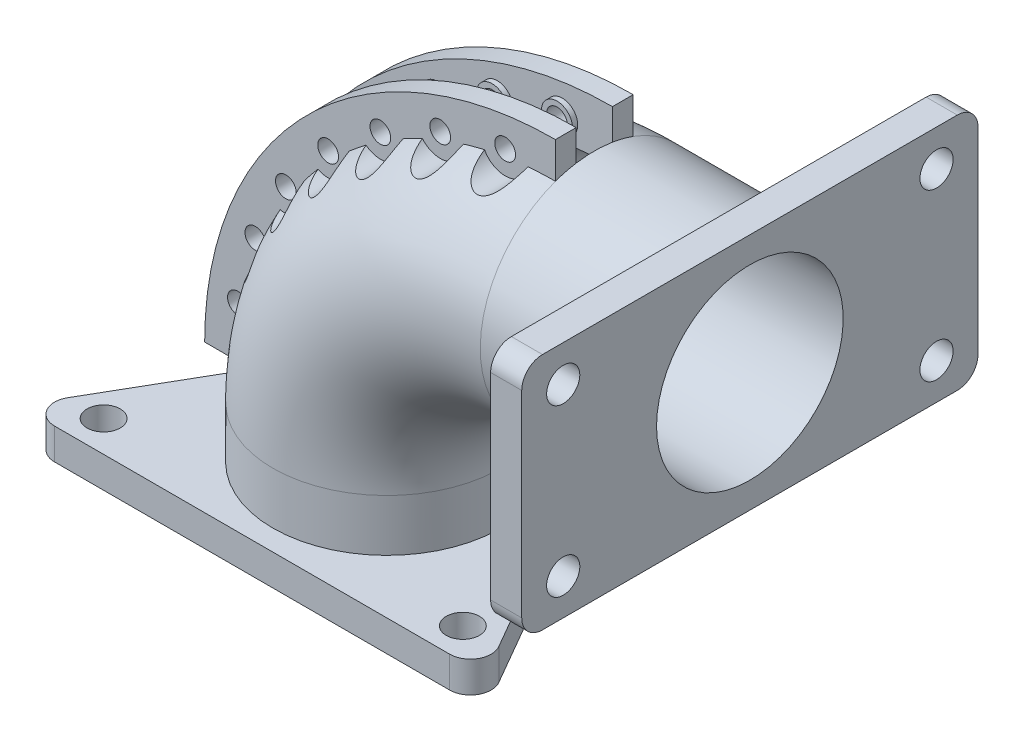
SolidWorks part; units mm, degrees
material "聚脂树脂"
ref_plane "前视基准面" through (0, 0, 0) normal (0, 0, 1) x (1, 0, 0)
ref_plane "上视基准面" through (0, 0, 0) normal (0, 1, 0) x (1, 0, 0)
ref_plane "右视基准面" through (0, 0, 0) normal (1, 0, 0) x (0, 0, -1)
sketch "草图1" plane through (0, 0, 0) normal (0, 1, 0) x (1, 0, 0)
  line L0 (0, 40) -> (0, 0) construction
  line L4 (0, 0) -> (-34.641, -20) construction
  line L5 (0, 0) -> (34.641, -20) construction
  line L6 (-1.7321, 23) -> (-20.7846, -10)
  line L7 (-19.0526, -13) -> (19.0526, -13)
  line L8 (20.7846, -10) -> (1.7321, 23)
  circle A0 centre (0, 0) radius 9
  circle A2 centre (0, 0) radius 20 construction
  circle A3 centre (0, 20) radius 1.6
  circle A4 centre (-17.3205, -10) radius 1.6
  circle A5 centre (17.3205, -10) radius 1.6
  arc A9 (-1.7321, 23) -> (1.7321, 23) centre (0, 22) cw
  arc A10 (19.0526, -13) -> (20.7846, -10) centre (19.0526, -11) ccw
  arc A11 (-20.7846, -10) -> (-19.0526, -13) centre (-19.0526, -11) ccw
  point P18 (0, 26)
  point P21 (22.5167, -13)
  point P24 (-22.5167, -13)
  dimension "D1" = 18
  dimension "D2" = 40
  dimension "D3" = 3.2
  dimension "D4" = 120
  dimension "D5" = 3.2
  dimension "D6" = 120
  dimension "D7" = 3.2
  dimension "D8" = 26
  dimension "D10" = 2
  dimension "D9" = 26
extrude "凸台-拉伸1" add sketch "草图1" along normal blind 3
sketch "草图2" plane through (0, 3, 0) normal (0, 1, 0) x (1, 0, 0)
  circle A0 centre (0, 0) radius 9
  circle A1 centre (0, 0) radius 11
  dimension "D1" = 22
  dimension "D2" = 18
sketch "草图3" plane through (0, 0, 0) normal (0, 0, 1) x (1, 0, 0)
  line L0 (0, 3) -> (0, 8)
  line L1 (11, 3) -> (-11, 3) construction
  line L2 (20, 28) -> (20, 8) construction
  line L3 (20, 28) -> (35, 28)
  arc A0 (0, 8) -> (20, 28) centre (20, 8) cw
  dimension "D1" = 5
  dimension "D2" = 20
  dimension "D3" = 15
sweep "扫描1" add profiles "草图2" path "草图3"
sketch "草图4" plane through (35, 0, 0) normal (1, 0, 0) x (0, 0, -1)
  line L0 (0, 28) -> (0, 37.8313) construction
  line L1 (20, 16.5) -> (-20, 16.5)
  line L2 (22, 18.5) -> (22, 37.5)
  line L3 (20, 39.5) -> (-20, 39.5)
  line L4 (-22, 18.5) -> (-22, 37.5)
  line L5 (22, 16.5) -> (-22, 39.5) construction
  line L6 (22, 39.5) -> (-22, 16.5) construction
  line L7 (0, 28) -> (4.7838, 28) construction
  circle A0 centre (0, 28) radius 9
  circle A1 centre (-18, 36) radius 1.6
  circle A2 centre (18, 36) radius 1.6
  circle A3 centre (-18, 20) radius 1.6
  circle A4 centre (18, 20) radius 1.6
  arc A5 (22, 37.5) -> (20, 39.5) centre (20, 37.5) ccw
  arc A6 (20, 16.5) -> (22, 18.5) centre (20, 18.5) ccw
  arc A7 (-20, 16.5) -> (-22, 18.5) centre (-20, 18.5) cw
  arc A8 (-20, 39.5) -> (-22, 37.5) centre (-20, 37.5) ccw
  dimension "D1" = 18
  dimension "D4" = 3.2
  dimension "D7" = 2
  dimension "D2" = 44
  dimension "D3" = 23
  dimension "D5" = 8
  dimension "D6" = 18
extrude "凸台-拉伸3" add sketch "草图4" against normal blind 3
sketch "草图5" plane through (0, 0, 0) normal (0, 0, 1) x (1, 0, 0)
  line L0 (-11, 8) -> (-11, 3) construction
  line L4 (11, 8) -> (-11, 8) construction
  line L5 (20, 17) -> (20, 39) construction
  line L6 (32, 39) -> (20, 39) construction
  line L7 (-8, 8) -> (-14.303, 8)
  line L8 (20, 47.0087) -> (20, 36)
  arc A0 (-8, 8) -> (20, 36) centre (20, 8) cw
  arc A1 (-14.303, 8) -> (20, 47.0087) centre (25.0284, 8) cw
  dimension "D1" = 3
  dimension "D2" = 3
extrude "切除-拉伸1" cut sketch "草图5" against normal blind 1.75 and the other way blind 1.75
sketch "草图6" plane through (0, 0, -1.75) normal (0, 0, 1) x (1, 0, 0)
  line L0 (20, 36.8282) -> (20, 41.8282)
  line L1 (-13.8282, 8) -> (-8.8282, 8)
  arc A0 (20, 36.8282) -> (-8.8282, 8) centre (20, 8) ccw construction
  arc A1 (20, 36.8282) -> (-8.8282, 8) centre (20, 8) ccw
  arc A2 (20, 41.8282) -> (-13.8282, 8) centre (20, 8) ccw
  dimension "D1" = 5
  dimension "D2" = 5
extrude "凸台-拉伸4" add sketch "草图6" against normal blind 2
sketch "草图7" plane through (0, 0, 1.75) normal (0, 0, -1) x (-1, 0, 0)
  line L0 (-20, 36.8282) -> (-20, 41.8282)
  line L1 (13.8282, 8) -> (8.8282, 8)
  arc A0 (8.8282, 8) -> (-20, 36.8282) centre (-20, 8) ccw construction
  arc A1 (8.8282, 8) -> (-20, 36.8282) centre (-20, 8) ccw
  arc A2 (-20, 41.8282) -> (13.8282, 8) centre (-20, 8) cw
  dimension "D1" = 5
  dimension "D2" = 5
extrude "凸台-拉伸5" add sketch "草图7" against normal blind 2
sketch "草图8" plane through (0, 0, 3.75) normal (0, 0, 1) x (1, 0, 0)
  line L0 (20, 39) -> (20, 9.0901) construction
  line L1 (-10.8599, 8) -> (20, 8) construction
  line L2 (20, 8) -> (15.1505, 38.6183) construction
  line L3 (8.8906, 36.941) -> (20, 8) construction
  line L4 (20, 8) -> (8.8906, 36.941) construction
  line L5 (20, 8) -> (3.1162, 33.9988) construction
  circle A0 centre (20, 8) radius 31 construction
  circle A1 centre (15.1505, 38.6183) radius 1
  circle A2 centre (15.1505, 38.6183) radius 2.5 construction
  circle A3 centre (8.8906, 36.941) radius 1
  circle A4 centre (8.8906, 36.941) radius 2.5 construction
  circle A5 centre (3.1162, 33.9988) radius 1
  circle A6 centre (-1.9203, 29.9203) radius 1
  circle A7 centre (-5.9988, 24.8838) radius 1
  circle A8 centre (-8.941, 19.1094) radius 1
  circle A9 centre (-10.6183, 12.8495) radius 1
  dimension "D1" = 2
  dimension "D2" = 5
  dimension "D3" = 2
  dimension "D4" = 5
  dimension "D5" = 12
  dimension "D6" = 9
  dimension "D8" = 12
  dimension "D7" = 6
extrude "切除-拉伸2" cut sketch "草图8" against normal through all both and the other way through all
sketch "草图9" plane through (0, 0, 3.75) normal (0, 0, 1) x (1, 0, 0)
  circle A0 centre (15.1505, 38.6183) radius 2.25
  circle A1 centre (8.8906, 36.941) radius 2.25
  circle A2 centre (3.1162, 33.9988) radius 2.25
  circle A3 centre (-1.9203, 29.9203) radius 2.25
  circle A4 centre (-5.9988, 24.8838) radius 2.25
  circle A5 centre (-8.941, 19.1094) radius 2.25
  circle A6 centre (-10.6183, 12.8495) radius 2.25
  dimension "D1" = 4.5
  dimension "D2" = 4.5
  dimension "D3" = 4.5
  dimension "D4" = 4.5
  dimension "D5" = 4.5
  dimension "D6" = 4.5
  dimension "D7" = 4.5
extrude "切除-拉伸3" cut sketch "草图9" along normal through all
sketch "草图10" plane through (0, 0, -3.75) normal (0, 0, -1) x (-1, 0, 0)
  circle A1 centre (5.9988, 24.8838) radius 2.25
  circle A2 centre (5.9988, 24.8838) radius 2.25
  circle A3 centre (1.9203, 29.9203) radius 2.25
  circle A4 centre (1.9203, 29.9203) radius 2.25
  circle A5 centre (-3.1162, 33.9988) radius 2.25
  circle A6 centre (-3.1162, 33.9988) radius 2.25
  circle A7 centre (-8.8906, 36.941) radius 2.25
  circle A8 centre (-8.8906, 36.941) radius 2.25
  circle A9 centre (-15.1505, 38.6183) radius 2.25
  circle A10 centre (-15.1505, 38.6183) radius 2.25
  circle A11 centre (10.6183, 12.8495) radius 2.25
  circle A12 centre (10.6183, 12.8495) radius 2.25
  circle A13 centre (8.941, 19.1094) radius 2.25
  circle A14 centre (8.941, 19.1094) radius 2.25
  dimension "D1" = 0
  dimension "D2" = 0
  dimension "D3" = 0
  dimension "D4" = 0
  dimension "D5" = 0
  dimension "D6" = 0
  dimension "D7" = 0
extrude "切除-拉伸4" cut sketch "草图10" along normal through all
sketch "草图11" plane through (0, 0, -1.75) normal (0, 0, 1) x (1, 0, 0)
  circle A0 centre (15.1505, 38.6183) radius 1
  circle A1 centre (15.1505, 38.6183) radius 1.5
  circle A2 centre (8.8906, 36.941) radius 1
  circle A3 centre (8.8906, 36.941) radius 1.5
  circle A4 centre (3.1162, 33.9988) radius 1
  circle A5 centre (3.1162, 33.9988) radius 1.5
  circle A6 centre (-1.9203, 29.9203) radius 1
  circle A7 centre (-1.9203, 29.9203) radius 1.5
  circle A8 centre (-5.9988, 24.8838) radius 1
  circle A9 centre (-5.9988, 24.8838) radius 1.5
  circle A10 centre (-8.941, 19.1094) radius 1
  circle A11 centre (-8.941, 19.1094) radius 1.5
  circle A12 centre (-10.6183, 12.8495) radius 1
  circle A13 centre (-10.6183, 12.8495) radius 1.5
  dimension "D1" = 2
  dimension "D2" = 3
  dimension "D3" = 2
  dimension "D4" = 3
  dimension "D5" = 2
  dimension "D6" = 3
  dimension "D7" = 3
  dimension "D8" = 2
  dimension "D9" = 2
  dimension "D10" = 3
  dimension "D11" = 3
  dimension "D12" = 2
  dimension "D13" = 2
  dimension "D14" = 3
extrude "凸台-拉伸6" add sketch "草图11" along normal blind 0.5
sketch "草图12" plane through (0, 0, 1.75) normal (0, 0, -1) x (-1, 0, 0)
  circle A1 centre (1.9203, 29.9203) radius 1.5
  circle A2 centre (1.9203, 29.9203) radius 1.5
  circle A3 centre (1.9203, 29.9203) radius 1
  circle A4 centre (1.9203, 29.9203) radius 1
  circle A5 centre (-3.1162, 33.9988) radius 1.5
  circle A6 centre (-3.1162, 33.9988) radius 1.5
  circle A7 centre (-3.1162, 33.9988) radius 1
  circle A8 centre (-3.1162, 33.9988) radius 1
  circle A9 centre (-8.8906, 36.941) radius 1.5
  circle A10 centre (-8.8906, 36.941) radius 1.5
  circle A11 centre (-8.8906, 36.941) radius 1
  circle A12 centre (-8.8906, 36.941) radius 1
  circle A13 centre (-15.1505, 38.6183) radius 1.5
  circle A14 centre (-15.1505, 38.6183) radius 1.5
  circle A15 centre (-15.1505, 38.6183) radius 1
  circle A16 centre (-15.1505, 38.6183) radius 1
  circle A17 centre (10.6183, 12.8495) radius 1.5
  circle A18 centre (10.6183, 12.8495) radius 1.5
  circle A19 centre (10.6183, 12.8495) radius 1
  circle A20 centre (10.6183, 12.8495) radius 1
  circle A21 centre (8.941, 19.1094) radius 1.5
  circle A22 centre (8.941, 19.1094) radius 1.5
  circle A23 centre (8.941, 19.1094) radius 1
  circle A24 centre (8.941, 19.1094) radius 1
  circle A25 centre (5.9988, 24.8838) radius 1.5
  circle A26 centre (5.9988, 24.8838) radius 1.5
  circle A27 centre (5.9988, 24.8838) radius 1
  circle A28 centre (5.9988, 24.8838) radius 1
  dimension "D1" = 0
  dimension "D2" = 0
  dimension "D3" = 0
  dimension "D4" = 0
  dimension "D5" = 0
  dimension "D6" = 0
  dimension "D7" = 0
  dimension "D8" = 0
  dimension "D9" = 0
  dimension "D10" = 0
  dimension "D11" = 0
  dimension "D12" = 0
  dimension "D13" = 0
  dimension "D14" = 0
extrude "凸台-拉伸7" add sketch "草图12" along normal blind 0.5
